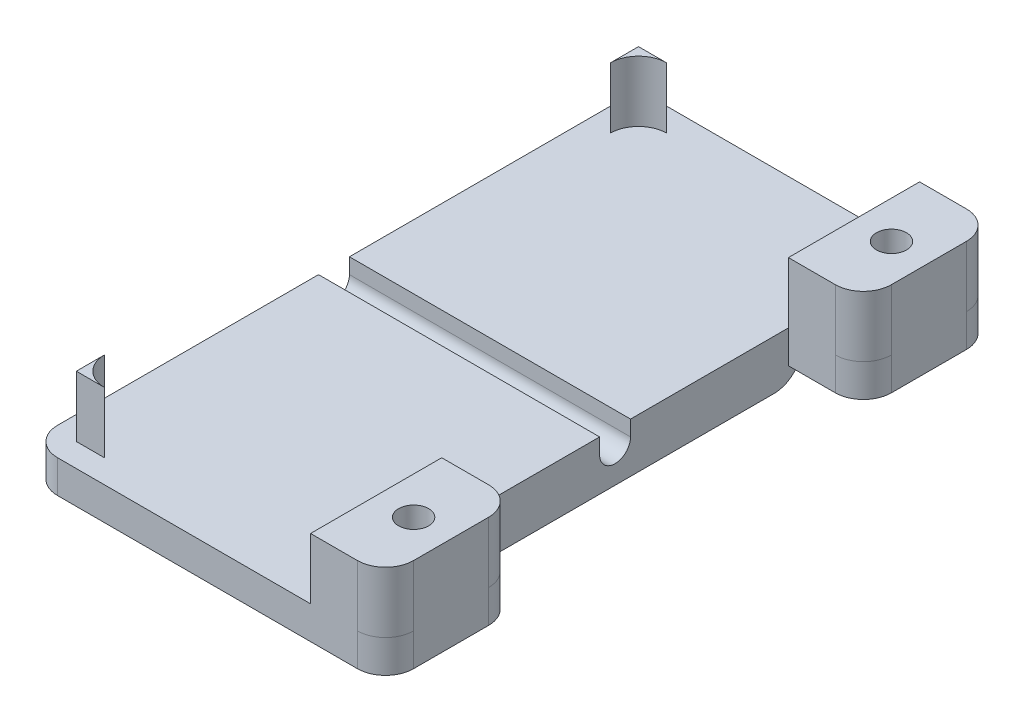
SolidWorks part; units mm, degrees
ref_plane "Plan de face" through (0, 0, 0) normal (0, 0, 1) x (1, 0, 0)
ref_plane "Plan de dessus" through (0, 0, 0) normal (0, 1, 0) x (1, 0, 0)
ref_plane "Plan de droite" through (0, 0, 0) normal (1, 0, 0) x (0, 0, -1)
sketch "Esquisse1" plane through (0, 0, 0) normal (0, 0, 1) x (1, 0, 0)
  line L1 (-15, -5) -> (15, -5)
  line L2 (-15, -5) -> (-15, 5)
  line L3 (-15, 5) -> (15, 5)
  line L4 (15, -5) -> (15, 5)
  line L5 (-15, -5) -> (15, 5) construction
  line L6 (-15, 5) -> (15, -5) construction
  point P0 (0, 0)
  dimension "D1" = 30
  dimension "D2" = 10
extrude "Boss.-Extru.1" add sketch "Esquisse1" along normal blind 65
sketch "Esquisse2" plane through (0, 5, 0) normal (0, 1, 0) x (1, 0, 0)
  line L0 (-15, -65) -> (-15, 0) construction
  line L1 (-15, -14) -> (-12.5, -14)
  line L2 (-15, -14) -> (-15, -51)
  line L3 (-15, -51) -> (-12.5, -51)
  line L5 (15, -65) -> (15, 0) construction
  line L6 (-12.5, -51) -> (-12.5, -62.5)
  line L7 (15, -2.5) -> (-12.5, -2.5)
  line L8 (15, -2.5) -> (15, -62.5)
  line L9 (15, -62.5) -> (-12.5, -62.5)
  line L10 (-12.5, -2.5) -> (-12.5, -14)
  point P6 (-15, -32.5)
  dimension "D1" = 37
  dimension "D2" = 2.5
  dimension "D3" = 60
extrude "Enlèv. mat.-Extru.1" cut sketch "Esquisse2" against normal blind 6.5
sketch "Esquisse3" plane through (15, 0, 0) normal (1, 0, 0) x (0, 0, -1)
  line L0 (-62.5, -1.5) -> (-2.5, -1.5) construction
  line L1 (-65, -5) -> (-51, -5)
  line L2 (-65, -5) -> (-65, -1.5)
  line L3 (-65, -1.5) -> (-51, -1.5)
  line L4 (-51, -5) -> (-51, -1.5)
  line L5 (-51, -1.5) -> (-62.5, -1.5) construction
  line L7 (-14, -1.5) -> (0, -1.5)
  line L8 (-14, -1.5) -> (-14, -5)
  line L9 (-14, -5) -> (0, -5)
  line L10 (0, -1.5) -> (0, -5)
extrude "Boss.-Extru.2" add sketch "Esquisse3" along normal blind 8
sketch "Esquisse4" plane through (0, -1.5, 0) normal (0, 1, 0) x (1, 0, 0)
  line L0 (19, -7) -> (19, -58) construction
  line L1 (-15, -14) -> (-15, -51) construction
  line L2 (23, 0) -> (23, -14) construction
  line L3 (23, 0) -> (15, 0) construction
  circle A0 centre (19, -7) radius 1.6
  circle A1 centre (19, -58) radius 1.6
  point P2 (19, -32.5)
  point P5 (-15, -32.5)
  point P8 (23, -7)
  point P11 (19, 0)
  dimension "D1" = 3.2
extrude "Enlèv. mat.-Extru.2" cut sketch "Esquisse4" against normal blind 4
fillet "Congé1" radius 3 6 edges at (-15, 0, 0) (-15, 0, 65) (23, -3.25, 65) (23, -3.25, 0) (23, -3.25, 14) (23, -3.25, 51)
sketch "Esquisse5" plane through (0, 0, 65) normal (0, 0, 1) x (1, 0, 0)
  line L0 (-15, -5) -> (75, -5) construction
  line L1 (75, -5) -> (75, -66) construction
  line L3 (75, -66) -> (70, -66) construction
  line L4 (75, -66) -> (75, -91)
  line L5 (75, -91) -> (70, -91)
  line L6 (70, -66) -> (70, -91) construction
  line L7 (20, -1.5) -> (15, -1.5) construction
  line L8 (13.3674, -1.5) -> (15, -1.5)
  line L9 (15, -1.5) -> (15, 5) construction
  line L10 (15, -1.5) -> (-15, -5)
  circle A0 centre (-24.0415, -98.9422) radius 94.3763 construction
  circle A1 centre (-24.0415, -98.9422) radius 104.3763 construction
  arc A2 (70, -91) -> (-15, -5) centre (-24.0415, -98.9422) ccw
  arc A3 (75, -66) -> (13.3674, -1.5) centre (-24.0415, -98.9422) ccw
  line M4 (-12, 5) -> (-12, -5)
  line M5 (-12, -5) -> (20, -5)
  line M6 (20, -5) -> (20, -1.5)
  dimension "D5" = 10
  dimension "D1" = 90
  dimension "D2" = 61
  dimension "D3" = 5
  dimension "D4" = 25
extrude "Boss.-Extru.3" [suppressed] add sketch "Esquisse5" against normal blind 5 and the other way blind 5 from offset 32.5 contours L4 A3 L10 A2 L5 M6 M5 M4 offset against normal yes
sketch "Esquisse6" [suppressed] plane through (0, -5, 0) normal (0, 1, 0) x (1, 0, 0)
  line L1 (20, -27.5) -> (15, -27.5)
  line L2 (20, -27.5) -> (20, -37.5)
  line L3 (20, -37.5) -> (15, -37.5)
  line L4 (15, -27.5) -> (15, -37.5)
extrude "Boss.-Extru.4" [suppressed] add sketch "Esquisse6" along normal blind 3.5
sketch "Esquisse7" [suppressed] plane through (75, 0, 0) normal (1, 0, 0) x (0, 0, -1)
  line L0 (-37.5, -66) -> (-27.5, -66) construction
  line L1 (-42.5, -83.5) -> (-22.5, -83.5) construction
  line L2 (-42.5, -83.5) -> (-42.5, -73.5) construction
  line L3 (-42.5, -73.5) -> (-22.5, -73.5) construction
  line L4 (-22.5, -83.5) -> (-22.5, -73.5) construction
  line L5 (-42.5, -83.5) -> (-22.5, -73.5) construction
  line L6 (-42.5, -73.5) -> (-22.5, -83.5) construction
  line L7 (-37.5, -91) -> (-27.5, -91) construction
  line L9 (-47.5, -91) -> (-17.5, -91)
  line L10 (-47.5, -91) -> (-47.5, -68.5)
  line L11 (-47.5, -68.5) -> (-17.5, -68.5)
  line L12 (-17.5, -91) -> (-17.5, -68.5)
  circle A0 centre (-42.5, -73.5) radius 1.6
  circle A1 centre (-22.5, -73.5) radius 1.6
  circle A2 centre (-22.5, -83.5) radius 1.6
  circle A3 centre (-42.5, -83.5) radius 1.6
  point P0 (-32.5, -78.5)
  point P8 (-32.5, -66)
  point P18 (-32.5, -91)
  dimension "D3" = 3.2
  dimension "D1" = 20
  dimension "D2" = 10
  dimension "D4" = 7.5
  dimension "D5" = 5
  dimension "D6" = 5
extrude "Boss.-Extru.5" [suppressed] add sketch "Esquisse7" against normal blind 5
sketch "Esquisse8" [suppressed] plane through (70, 0, 0) normal (1, 0, 0) x (0, 0, -1)
  line L1 (-40.8834, -70.7) -> (-44.1166, -70.7)
  line L2 (-44.1166, -70.7) -> (-45.7332, -73.5)
  line L3 (-45.7332, -73.5) -> (-44.1166, -76.3)
  line L4 (-44.1166, -76.3) -> (-40.8834, -76.3)
  line L5 (-40.8834, -76.3) -> (-39.2668, -73.5)
  line L6 (-39.2668, -73.5) -> (-40.8834, -70.7)
  line L7 (-20.8834, -70.7) -> (-24.1166, -70.7)
  line L8 (-24.1166, -70.7) -> (-25.7332, -73.5)
  line L9 (-25.7332, -73.5) -> (-24.1166, -76.3)
  line L10 (-24.1166, -76.3) -> (-20.8834, -76.3)
  line L11 (-20.8834, -76.3) -> (-19.2668, -73.5)
  line L12 (-19.2668, -73.5) -> (-20.8834, -70.7)
  line L13 (-20.8834, -86.3) -> (-19.2668, -83.5)
  line L14 (-19.2668, -83.5) -> (-20.8834, -80.7)
  line L15 (-20.8834, -80.7) -> (-24.1166, -80.7)
  line L16 (-24.1166, -80.7) -> (-25.7332, -83.5)
  line L17 (-25.7332, -83.5) -> (-24.1166, -86.3)
  line L18 (-24.1166, -86.3) -> (-20.8834, -86.3)
  line L19 (-40.8834, -86.3) -> (-39.2668, -83.5)
  line L20 (-39.2668, -83.5) -> (-40.8834, -80.7)
  line L21 (-40.8834, -80.7) -> (-44.1166, -80.7)
  line L22 (-44.1166, -80.7) -> (-45.7332, -83.5)
  line L23 (-45.7332, -83.5) -> (-44.1166, -86.3)
  line L24 (-44.1166, -86.3) -> (-40.8834, -86.3)
  circle A0 centre (-42.5, -73.5) radius 2.8 construction
  circle A1 centre (-22.5, -73.5) radius 2.8 construction
  circle A2 centre (-22.5, -83.5) radius 2.8 construction
  circle A3 centre (-42.5, -83.5) radius 2.8 construction
  dimension "D1" = 5.6
extrude "Enlèv. mat.-Extru.3" [suppressed] cut sketch "Esquisse8" along normal blind 2.5
fillet "Congé2" [suppressed] radius 3
fillet "Congé3" [suppressed] radius 3
fillet "Congé4" radius 3 2 edges at (-12.5, 1.75, 2.5) (-12.5, 1.75, 62.5)
sketch "Esquisse9" plane through (0, 5, 0) normal (0, 1, 0) x (1, 0, 0)
  line L0 (15, -51) -> (15, -14) construction
  line L1 (49.7076, -66.9887) -> (-19.7076, -66.9887)
  line L2 (49.7076, -66.9887) -> (49.7076, 1.9887)
  line L3 (49.7076, 1.9887) -> (-19.7076, 1.9887)
  line L4 (-19.7076, -66.9887) -> (-19.7076, 1.9887)
  line L5 (49.7076, -66.9887) -> (-19.7076, 1.9887) construction
  line L6 (49.7076, 1.9887) -> (-19.7076, -66.9887) construction
  line L8 (42.5, -62.5) -> (-12.5, -62.5)
  line L9 (42.5, -62.5) -> (42.5, -2.5)
  line L10 (42.5, -2.5) -> (-12.5, -2.5)
  line L11 (-12.5, -62.5) -> (-12.5, -2.5)
  line L12 (42.5, -62.5) -> (-12.5, -2.5) construction
  line L13 (42.5, -2.5) -> (-12.5, -62.5) construction
  point P0 (15, -32.5)
  point P7 (15, -32.5)
  point P14 (-12.5, -2.5)
extrude "Enlèv. mat.-Extru.5" cut sketch "Esquisse9" against normal blind 6.5
sketch "Esquisse10" plane through (0, -1.5, 0) normal (0, 1, 0) x (1, 0, 0)
  line L0 (23, -3) -> (23, -11) construction
  line L1 (15, -14) -> (23, -14)
  line L2 (15, -14) -> (15, 0)
  line L3 (15, 0) -> (23, 0)
  line L4 (23, -14) -> (23, 0)
  line L5 (15, -51) -> (23, -51)
  line L6 (15, -51) -> (15, -65)
  line L7 (15, -65) -> (23, -65)
  line L8 (23, -51) -> (23, -65)
  line L9 (20, -65) -> (-12, -65) construction
  line L10 (23, -54) -> (23, -62) construction
extrude "Boss.-Extru.6" add sketch "Esquisse10" along normal blind 6.5
fillet "Congé5" radius 3 4 edges at (23, 1.75, 65) (23, 1.75, 51) (23, 1.75, 14) (23, 1.75, 0)
sketch "Esquisse11" plane through (0, -1.5, 0) normal (0, -1, 0) x (1, 0, 0)
  circle A0 centre (19, 58) radius 1.6
  circle A1 centre (19, 7) radius 1.6
extrude "Enlèv. mat.-Extru.6" cut sketch "Esquisse11" against normal blind 6.5
sketch "Esquisse12" plane through (0, -5, 0) normal (0, -1, 0) x (1, 0, 0)
  line L1 (19, 54.7668) -> (21.8, 56.3834)
  line L2 (21.8, 56.3834) -> (21.8, 59.6166)
  line L3 (21.8, 59.6166) -> (19, 61.2332)
  line L4 (19, 61.2332) -> (16.2, 59.6166)
  line L5 (16.2, 59.6166) -> (16.2, 56.3834)
  line L6 (16.2, 56.3834) -> (19, 54.7668)
  line L7 (19, 3.7668) -> (21.8, 5.3834)
  line L8 (21.8, 5.3834) -> (21.8, 8.6166)
  line L9 (21.8, 8.6166) -> (19, 10.2332)
  line L10 (19, 10.2332) -> (16.2, 8.6166)
  line L11 (16.2, 8.6166) -> (16.2, 5.3834)
  line L12 (16.2, 5.3834) -> (19, 3.7668)
  circle A0 centre (19, 58) radius 2.8 construction
  circle A1 centre (19, 7) radius 2.8 construction
  dimension "D1" = 5.6
extrude "Enlèv. mat.-Extru.7" cut sketch "Esquisse12" against normal blind 2.5
sketch "Esquisse14" plane through (-15, 0, 0) normal (-1, 0, 0) x (0, 0, 1)
  line L1 (3, -1.5) -> (62, -1.5) construction
  line L2 (30.85, -3.15) -> (30.85, -1.5)
  line L3 (30.85, -1.5) -> (34.15, -1.5)
  line L4 (34.15, -1.5) -> (34.15, -3.15)
  arc A0 (30.85, -3.15) -> (34.15, -3.15) centre (32.5, -3.15) ccw
  point P6 (32.5, -1.5)
  dimension "D1" = 3.3
extrude "Enlèv. mat.-Extru.8" cut sketch "Esquisse14" against normal blind 31.5
sketch "Esquisse15" plane through (0, -5, 0) normal (0, -1, 0) x (1, 0, 0)
  line L0 (-15, 62) -> (-15, 3) construction
  line L1 (15, 51) -> (-15, 51)
  line L2 (15, 51) -> (15, 14)
  line L3 (15, 14) -> (-15, 14)
  line L4 (-15, 51) -> (-15, 14)
  line L5 (20, 14) -> (15, 14) construction
extrude "Boss.-Extru.7" add sketch "Esquisse15" along normal blind 1.8
fillet "Congé6" radius 3 2 edges at (0, -5, 51) (0, -5, 14)
fillet "Congé7" radius 3 2 edges at (0, -6.8, 14) (0, -6.8, 51)
